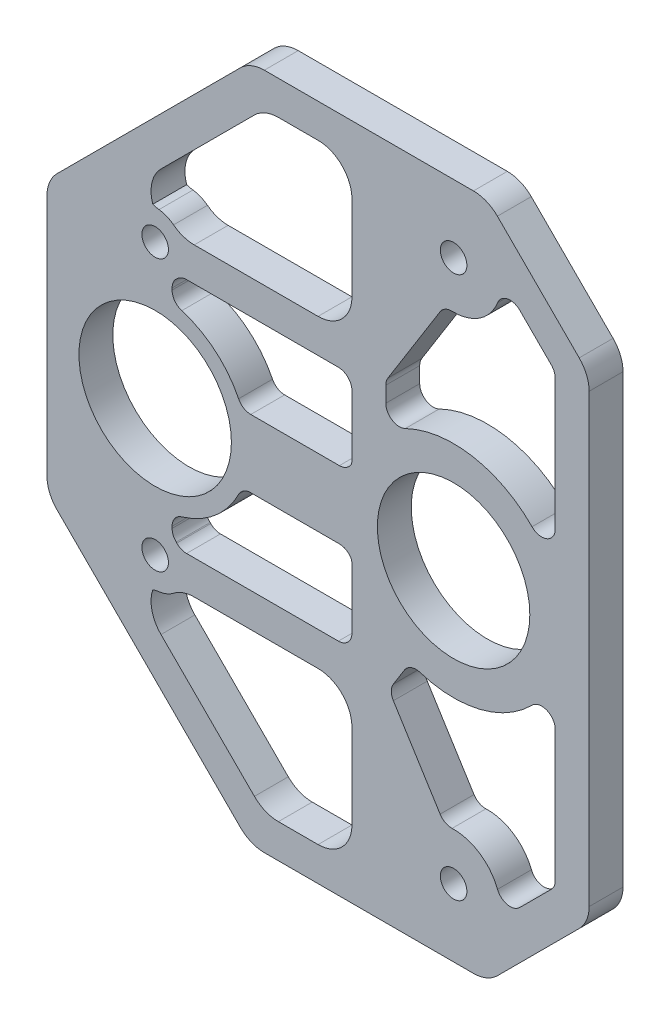
SolidWorks part; units mm, degrees
ref_plane "Front Plane" through (0, 0, 0) normal (0, 0, 1) x (1, 0, 0)
ref_plane "Top Plane" through (0, 0, 0) normal (0, 1, 0) x (1, 0, 0)
ref_plane "Right Plane" through (0, 0, 0) normal (1, 0, 0) x (0, 0, -1)
sketch "Sketch1" plane through (0, 0, 0) normal (0, 0, 1) x (1, 0, 0)
  line L1 (0, 0) -> (101.6, 0)
  line L2 (0, 0) -> (0, 127)
  line L3 (0, 127) -> (101.6, 127)
  line L4 (101.6, 0) -> (101.6, 127)
  circle A0 centre (20.2692, 88.9) radius 2.4892
  circle A1 centre (20.2692, 63.5) radius 14.2875
  circle A2 centre (20.2692, 38.1) radius 2.4892
  circle A3 centre (76.2, 114.3) radius 2.4892
  circle A4 centre (76.2, 63.5) radius 14.2875
  circle A5 centre (76.2, 12.7) radius 2.4892
  dimension "D3" = 25.4
  dimension "D10" = 25.4
  dimension "D12" = 4.9784
  dimension "D13" = 4.9784
  dimension "D14" = 28.575
  dimension "D15" = 28.575
  dimension "D16" = 4.9784
  dimension "D17" = 4.9784
  dimension "D2" = 101.6
  dimension "D4" = 63.5
  dimension "D5" = 50.8
  dimension "D6" = 50.8
  dimension "D7" = 12.7
  dimension "D8" = 25.4
  dimension "D9" = 25.4
  dimension "D11" = 127
  dimension "D18" = 55.9308
extrude "Boss-Extrude1" add sketch "Sketch1" along normal mid plane 6.35
chamfer "Chamfer2" distance 38.1 angle 45 2 edges at (0, 0, 0) (0, 127, 0)
chamfer "Chamfer3" distance 19.05 angle 45 2 edges at (101.6, 0, 0) (101.6, 127, 0)
fillet "Fillet2" radius 6.35 8 edges at (101.6, 107.95, 0) (82.55, 127, 0) (0, 88.9, 0) (0, 38.1, 0) (38.1, 0, 0) (82.55, 0, 0) (101.6, 19.05, 0) (38.1, 127, 0)
sketch "Sketch2" plane through (0, 0, 3.175) normal (0, 0, 1) x (1, 0, 0)
  line L0 (20.2692, 63.5) -> (76.2, 63.5) construction
  line L1 (76.2, 63.5) -> (101.6, 63.5) construction
  line L2 (101.6, 21.6803) -> (101.6, 105.3197) construction
  line L3 (101.6, 63.5) -> (0, 63.5) construction
  line L4 (0, 86.2697) -> (0, 40.7303) construction
  line L5 (20.2692, 63.5) -> (20.2692, 88.9) construction
  line L14 (20.2692, 88.9) -> (7.0515, 102.1177) construction
  line L15 (20.2692, 38.1) -> (6.35, 24.1808) construction
  line L16 (23.4442, 63.5) -> (23.4442, 88.9)
  line L17 (17.0942, 63.5) -> (17.0942, 88.9)
  line L18 (22.5143, 91.1451) -> (9.2966, 104.3628)
  line L19 (18.0241, 86.6549) -> (4.8064, 99.8726)
  line L20 (101.6, 69.85) -> (0, 69.85)
  line L21 (101.6, 57.15) -> (0, 57.15)
  line L22 (95.25, 21.6803) -> (95.25, 105.3197)
  line L23 (95.25, 105.3197) -> (79.9197, 120.65)
  line L24 (79.9197, 120.65) -> (40.7303, 120.65)
  line L25 (40.7303, 120.65) -> (6.35, 86.2697)
  line L26 (6.35, 86.2697) -> (6.35, 40.7303)
  line L27 (6.35, 40.7303) -> (40.7303, 6.35)
  line L28 (40.7303, 6.35) -> (79.9197, 6.35)
  line L29 (79.9197, 6.35) -> (95.25, 21.6803)
  line L30 (95.25, 21.6803) -> (95.25, 105.3197)
  line L31 (95.25, 105.3197) -> (79.9197, 120.65)
  line L32 (79.9197, 120.65) -> (40.7303, 120.65)
  line L33 (40.7303, 120.65) -> (6.35, 86.2697)
  line L34 (6.35, 86.2697) -> (6.35, 40.7303)
  line L35 (6.35, 40.7303) -> (40.7303, 6.35)
  line L36 (40.7303, 6.35) -> (79.9197, 6.35)
  line L37 (79.9197, 6.35) -> (95.25, 21.6803)
  line L38 (18.0241, 40.3451) -> (4.1049, 26.4259)
  line L39 (22.5143, 35.8549) -> (8.5951, 21.9357)
  line L40 (20.2692, 38.1) -> (20.2692, 63.5) construction
  line L41 (23.4442, 38.1) -> (23.4442, 63.5)
  line L42 (17.0942, 38.1) -> (17.0942, 63.5)
  line L43 (60.325, 6.35) -> (60.325, 145.4483) construction
  line L44 (20.2692, 38.1) -> (60.325, 38.1) construction
  line L45 (60.325, 38.1) -> (76.2, 12.7) construction
  line L46 (60.325, 38.1) -> (76.2, 63.5) construction
  line L47 (20.2692, 88.9) -> (60.325, 88.9) construction
  line L48 (60.325, 88.9) -> (76.2, 114.3) construction
  line L49 (20.2692, 85.725) -> (62.0847, 85.725)
  line L50 (62.0847, 85.725) -> (78.8924, 112.6173)
  line L51 (63.5, 6.35) -> (63.5, 145.4483)
  line L52 (20.2692, 34.925) -> (60.325, 34.925)
  line L53 (63.0174, 36.4173) -> (78.8924, 61.8173)
  line L54 (57.6326, 36.4173) -> (73.5076, 11.0173)
  line L55 (20.2692, 92.075) -> (58.5653, 92.075)
  line L56 (58.5653, 92.075) -> (73.5076, 115.9827)
  line L57 (57.15, 6.35) -> (57.15, 145.4483)
  line L58 (20.2692, 41.275) -> (60.325, 41.275)
  line L59 (57.6326, 39.7827) -> (73.5076, 65.1827)
  line L60 (63.0174, 39.7827) -> (78.8924, 14.3827)
  circle A5 centre (20.2692, 63.5) radius 17.4625
  circle A6 centre (20.2692, 63.5) radius 17.4625
  circle A8 centre (76.2, 63.5) radius 20.6375
  circle A9 centre (76.2, 63.5) radius 20.6375
  circle A11 centre (20.2692, 88.9) radius 5.6642
  circle A12 centre (20.2692, 88.9) radius 5.6642
  circle A14 centre (76.2, 114.3) radius 8.8392
  circle A15 centre (76.2, 114.3) radius 8.8392
  circle A17 centre (20.2692, 38.1) radius 5.6642
  circle A18 centre (20.2692, 38.1) radius 5.6642
  circle A20 centre (76.2, 12.7) radius 8.8392
  circle A21 centre (76.2, 12.7) radius 8.8392
  dimension "D1" = 3.175
  dimension "D2" = 6.35
  dimension "D3" = 3.175
  dimension "D4" = 6.35
  dimension "D5" = 3.175
  dimension "D6" = 6.35
  dimension "D7" = 6.35
  dimension "D8" = 3.175
  dimension "D9" = 3.175
  dimension "D10" = 3.175
  dimension "D11" = 3.175
  dimension "D12" = 6.35
  dimension "D13" = 6.35
  dimension "D14" = 3.175
  dimension "D15" = 3.175
  dimension "D16" = 3.175
  dimension "D17" = 3.175
  dimension "D18" = 3.175
  dimension "D19" = 3.175
extrude "Cut-Extrude2" cut sketch "Sketch2" against normal through all contours A12 L16 A6 L20 L57 L49 | A18 L58 L57 L21 A6 L41 | A15 L50 L51 A9 L20 L30 L31 | A21 L37 L30 L21 A9 L53 L60 | A12 L55 L57 L32 L33 L18 | A18 L39 L35 L36 L57 L52 region at (42.9143, 78.5821, 3.175) region at (42.9143, 48.4179, 3.175) region at (82.4121, 93.8509, 3.175) region at (41.4889, 104.5249, 3.175) region at (41.4889, 22.4751, 3.175) region at (82.9462, 32.8457, 3.175)
fillet "Fillet11" radius 2.54 26 edges at (64.0691, 38.1, 0) (68.0848, 44.525, 0) (95.25, 55.5625, 0) (95.25, 21.6803, 0) (84.9384, 11.3686, 0) (74.5203, 21.3781, 0) (95.25, 105.3197, 0) (95.25, 71.4375, 0) (63.5, 79.767, 0) (74.5203, 105.6219, 0) (84.9384, 115.6314, 0) (63.5, 87.9894, 0) (57.15, 85.725, 0) (57.15, 71.4375, 0) (56.5637, 69.85, 0) (23.4442, 80.6714, 0) (23.4442, 84.2093, 0) (24.9599, 85.725, 0) (36.5362, 69.85, 0) (23.4442, 46.3286, 0) (36.5362, 57.15, 0) (56.5637, 57.15, 0) (57.15, 55.5625, 0) (57.15, 41.275, 0) (23.4442, 42.7907, 0) (24.9599, 41.275, 0)
fillet "Fillet12" radius 6.35 12 edges at (57.15, 34.925, 0) (57.15, 6.35, 0) (16.8698, 30.2105, 0) (19.1974, 32.5381, 0) (24.9599, 34.925, 0) (40.7303, 6.35, 0) (16.8698, 96.7895, 0) (40.7303, 120.65, 0) (57.15, 120.65, 0) (57.15, 92.075, 0) (19.1974, 94.4619, 0) (24.9599, 92.075, 0)
